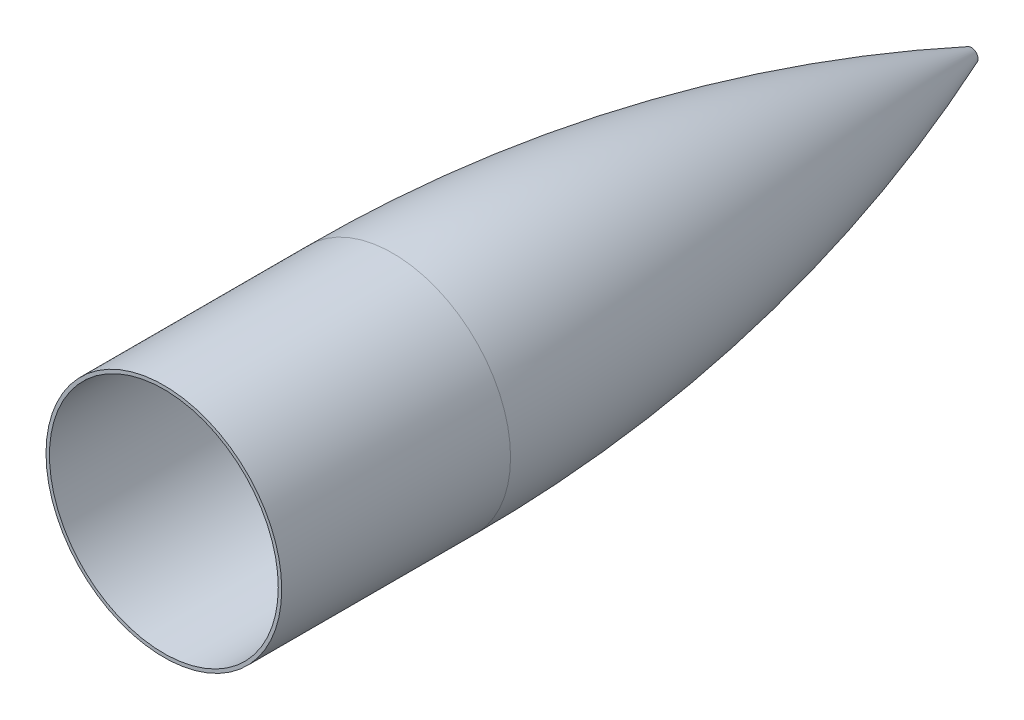
SolidWorks part; units mm, degrees
ref_plane "Front Plane" through (0, 0, 0) normal (0, 0, 1) x (1, 0, 0)
ref_plane "Top Plane" through (0, 0, 0) normal (0, 1, 0) x (1, 0, 0)
ref_plane "Right Plane" through (0, 0, 0) normal (1, 0, 0) x (0, 0, -1)
sketch "Sketch1" plane through (0, 0, 0) normal (0, 1, 0) x (1, 0, 0)
  line L0 (0, 431.8) -> (0, 101.6)
  line L1 (65.405, 101.6) -> (0, 101.6)
  line L4 (65.405, 101.6) -> (65.405, 15.3318) construction
  arc A0 (0, 431.8) -> (65.405, 101.6) centre (-800.8121, 101.6) cw
  point P10 (65.405, 101.6)
  dimension "D1" = 330.2
  dimension "D2" = 65.405
revolve "Revolve1" add sketch "Sketch1" angle 360 about L0
shell "Shell1" thickness 6.35 removed face at (-65.405, 0, -101.6)
ref_plane "Plane1" through (0, 0, -407.2807) normal (0, 0, 1) x (1, 0, 0)
sketch "Sketch2" plane through (0, 0, -407.2807) normal (0, 0, 1) x (1, 0, 0)
  line L1 (0, 6.0766) -> (-5.2625, 3.0383)
  line L2 (-5.2625, 3.0383) -> (-5.2625, -3.0383)
  line L3 (-5.2625, -3.0383) -> (0, -6.0766)
  line L4 (0, -6.0766) -> (5.2625, -3.0383)
  line L5 (5.2625, -3.0383) -> (5.2625, 3.0383)
  line L6 (5.2625, 3.0383) -> (0, 6.0766)
  circle A0 centre (0, 0) radius 5.2625 construction
  dimension "D1" = 10.525
extrude "Cut-Extrude1" cut sketch "Sketch2" along normal through all
sketch "Sketch3" plane through (0, 0, -407.2807) normal (0, 0, 1) x (1, 0, 0)
  circle A0 centre (0, 0) radius 3.675
  dimension "D1" = 7.35
extrude "Cut-Extrude2" cut sketch "Sketch3" against normal through all
sketch "Sketch8" plane through (0, 0, -101.6) normal (0, 0, 1) x (1, 0, 0)
  circle A0 centre (0, 0) radius 65.405
  circle A1 centre (0, 0) radius 52.705
  dimension "D1" = 130.81
  dimension "D2" = 12.7
extrude "Boss-Extrude1" add sketch "Sketch8" along normal blind 127
sketch "Sketch9" plane through (0, 0, 25.4) normal (0, 0, 1) x (1, 0, 0)
  circle A0 centre (0, 0) radius 2.5
  circle A1 centre (0, 0) radius 63.5
  dimension "D1" = 127
  dimension "D2" = 5
extrude "Cut-Extrude4" cut sketch "Sketch9" against normal blind 127
